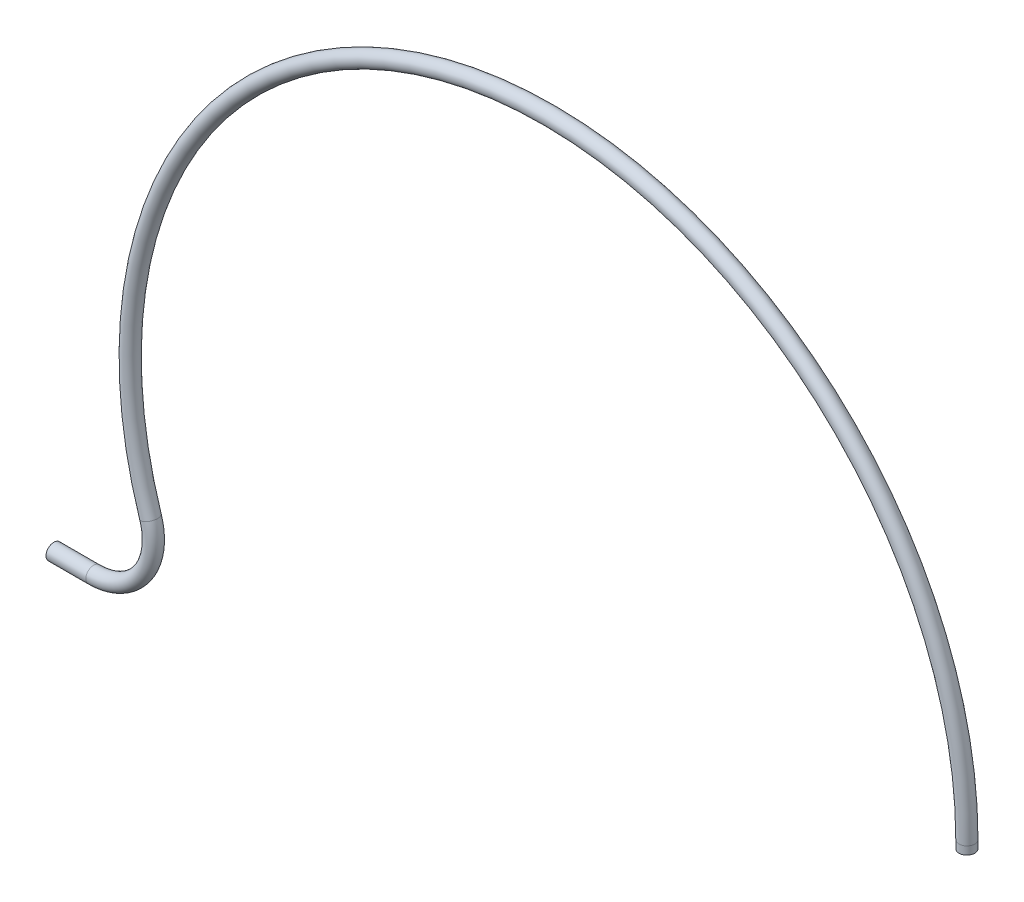
SolidWorks part; units mm, degrees
ref_plane "Front Plane" through (0, 0, 0) normal (0, 0, 1) x (1, 0, 0)
ref_plane "Top Plane" through (0, 0, 0) normal (0, 1, 0) x (1, 0, 0)
ref_plane "Right Plane" through (0, 0, 0) normal (1, 0, 0) x (0, 0, -1)
sketch "Sketch1" plane through (0, 0, 0) normal (0, 0, 1) x (1, 0, 0)
  line L0 (-99.178, -43.1051) -> (-89.178, -43.1051)
  line L1 (130.1891, 8.8628) -> (130.1891, 6.8628)
  line L2 (130.1891, -4.1051) -> (130.1891, -25.1051) construction
  line L6 (-115.8857, -43.1051) -> (-116.439, -43.1051) construction
  arc A0 (-89.178, -43.1051) -> (-74.9063, -23.4879) centre (-89.178, -28.1051) ccw
  arc A1 (-74.9063, -23.4879) -> (130.1891, 8.8628) centre (25.09, 8.8628) cw
  point P6 (126.5599, -3.032)
  point P7 (126.6026, 7.1041)
  point P9 (-73.8091, -24)
  point P10 (0, 0)
  point P14 (130.1891, 51.9524)
  point P15 (130.1891, 6.8628)
  dimension "D1" = 2
  dimension "D2" = 15
  dimension "D3" = 10
ref_plane "Plane1" through (-99.178, -43.1051, 0) normal (1, 0, 0) x (0, 0, -1)
sketch "Sketch2" plane through (-99.178, -43.1051, 0) normal (1, 0, 0) x (0, 0, -1)
  circle A2 centre (0, 0) radius 0.95
  circle A3 centre (0, 0) radius 1.975
  dimension "D1" = 1.9
  dimension "D2" = 3.95
sweep "Sweep1" add profiles "Sketch2" path "Sketch1"
